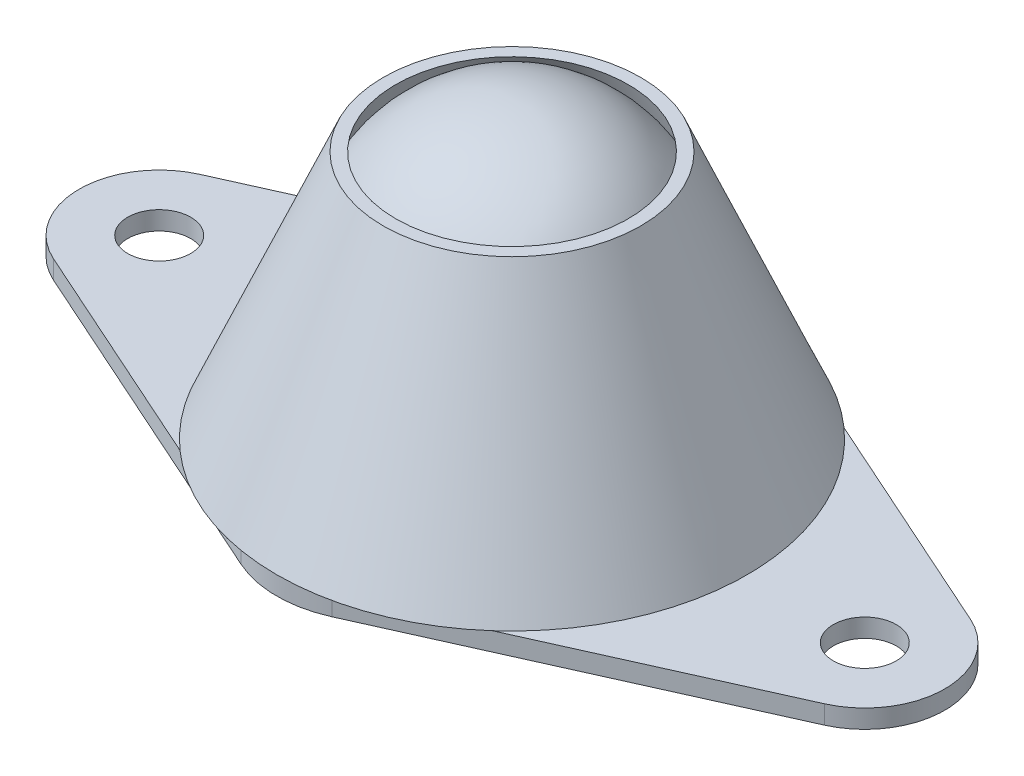
SolidWorks part; units mm, degrees
note: '?' marks a value the reader was unsure of.
ref_plane "Front Plane" through (0, 0, 0) normal (0, 0, 1) x (1, 0, 0)
ref_plane "Top Plane" through (0, 0, 0) normal (0, 1, 0) x (1, 0, 0)
ref_plane "Right Plane" through (0, 0, 0) normal (1, 0, 0) x (0, 0, -1)
sketch "Sketch1" plane through (0, 0, 0) normal (0, 1, 0) x (1, 0, 0)
  line L0 (-27.0798, 0) -> (27.0798, 0) construction
  line L1 (-19.05, 0) -> (19.05, 0) construction
  line L2 (-20.8177, 3.9446) -> (-2.4492, 12.1763)
  line L4 (-20.8177, -3.9446) -> (-2.4492, -12.1763)
  line L5 (0, -13.97) -> (0, 13.97) construction
  line L6 (20.8177, -3.9446) -> (2.4492, -12.1763)
  line L7 (20.8177, 3.9446) -> (2.4492, 12.1763)
  circle A0 centre (0, 0) radius 7.9375 construction
  arc A1 (20.8177, -3.9446) -> (20.8177, 3.9446) centre (19.05, 0) ccw
  arc A2 (-2.4492, 12.1763) -> (2.4492, 12.1763) centre (0, 6.7111) cw
  arc A3 (-20.8177, -3.9446) -> (-20.8177, 3.9446) centre (-19.05, 0) cw
  arc A4 (-2.4492, -12.1763) -> (2.4492, -12.1763) centre (0, -6.7111) ccw
  point P10 (0, 0)
  point P23 (0, 12.7)
  dimension "D1" = 15.875
  dimension "D3" = 12.7
  dimension "D2" = 38.1
extrude "Boss-Extrude1" add sketch "Sketch1" along normal blind 1 contours L4 A4 L6 A1 L7 A2 L2 A3
sketch "Sketch2" plane through (0, 0, 0) normal (0, 0, 1) x (1, 0, 0)
  line L0 (0, -13.97) -> (0, 13.97) construction
  line L1 (-20.8177, 1) -> (-23.3726, 1) construction
  line L2 (0, 16.875) -> (0, 1)
  line L3 (6.2801, 14.4384) -> (6.9516, 14.4384)
  line L4 (6.9516, 14.4384) -> (12.7, 1)
  line L5 (12.7, 1) -> (3.608, 1)
  line L6 (3.608, 1) -> (9.2588, 7.475)
  line L7 (9.2588, 7.475) -> (6.2801, 14.4384)
  arc A0 (0, 1) -> (0, 16.875) centre (0, 8.9375) ccw
  dimension "D1" = 15.875
  dimension "D2" = 0.6173
  dimension "D3" = 13.4384
  dimension "D4" = 3.608
  dimension "D5" = 12.7
ref_axis "Axis1" through (0, 17.7188, 0) along (0, -1, 0)?
revolve "Revolve3" add sketch "Sketch2" angle 360 about L2
hole_wizard "M3 Clearance Hole1" positions "Sketch4" profile "Sketch5" hole size "M3" standard "ANSI Metric" end condition through all
sketch "Sketch4" plane through (0, 0, 0) normal (0, -1, 0) x (-1, 0, 0)
  point P0 (-19.05, 0)
  point P3 (19.05, 0)
sketch "Sketch5" plane through (19.05, 0, 0) normal (1, 0, 0) x (0, 0, -1)
  line L0 (0, 0) -> (0, 16.875)
  line L1 (0, 16.875) -> (1.7, 16.875)
  line L2 (1.7, 16.875) -> (1.7, 0)
  line L5 (1.7, 0) -> (0, 0)
  line L11 (0, -6.35) -> (0, 107.95) construction
  dimension "Thru Hole Dia." = 3.4
  dimension "Thru Hole Depth" = 16.875
